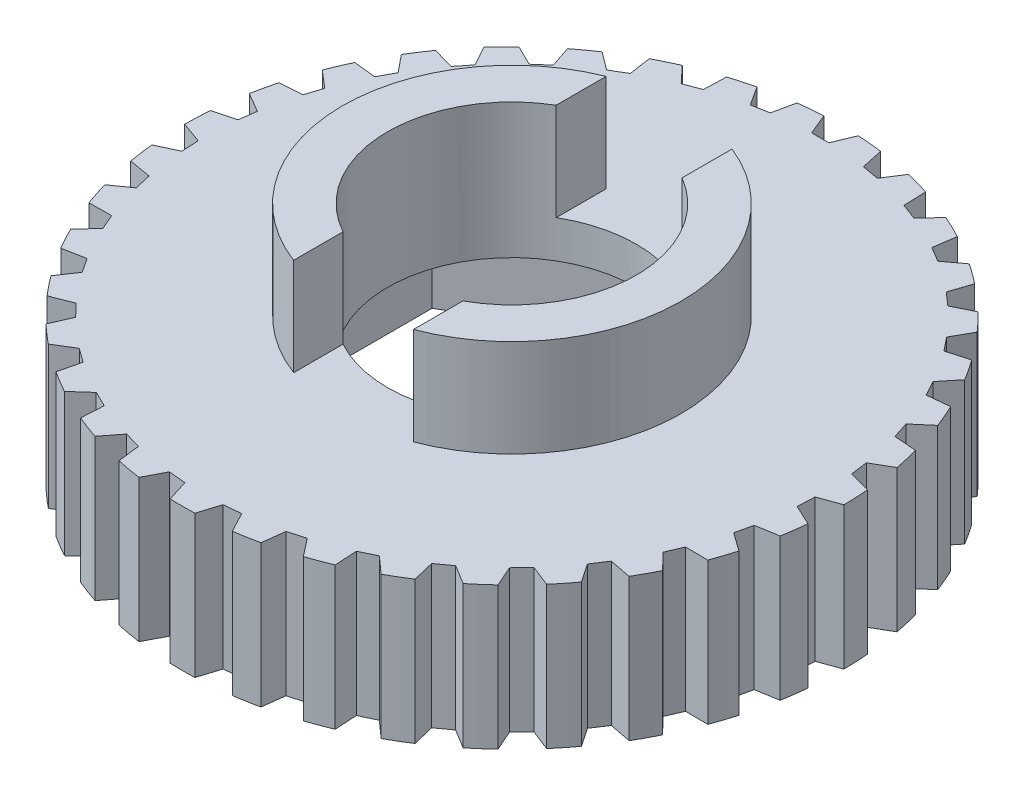
SolidWorks part; units mm, degrees
other "标注1"
sketch "草图6" plane through (10.9997, 0, -10.985) normal (0.2171, -0.5791, -0.7858) x (0.9761, 0.1195, 0.1816)
ref_plane "前视基准面" through (0, 0, 0) normal (0, 0, 1) x (1, 0, 0)
ref_plane "上视基准面" through (0, 0, 0) normal (0, 1, 0) x (1, 0, 0)
ref_plane "右视基准面" through (0, 0, 0) normal (1, 0, 0) x (0, 0, -1)
sketch "草图1" plane through (0, 0, 0) normal (0, 1, 0) x (1, 0, 0)
  circle A0 centre (0, 0) radius 5.65
  circle A1 centre (0, 0) radius 11
  circle A2 centre (0, 0) radius 4.15
  dimension "D1" = 11.3
  dimension "D2" = 22
  dimension "D3" = 1.5
extrude "凸台-拉伸1" add sketch "草图1" along normal blind 8 contours A0 A2 region at (-5.4902, 0, 0)
extrude "凸台-拉伸2" add sketch "草图1<3>" along normal blind 4.75 contours A1 A0 region at (-10.6889, 0, 0)
sketch "草图1<3>" plane through (0, 0, 0) normal (0, 1, 0) x (1, 0, 0) same geometry as "草图1"
sketch "草图2" plane through (0, 0, 0) normal (0, -1, 0) x (1, 0, 0)
  line L0 (-6, -3.4641) -> (-6, 3.4641) construction
  line L1 (-6, 3.4641) -> (0, 6.9282) construction
  line L2 (0, 6.9282) -> (6, 3.4641) construction
  line L3 (6, 3.4641) -> (6, -3.4641) construction
  line L4 (6, -3.4641) -> (0, -6.9282) construction
  line L5 (0, -6.9282) -> (-6, -3.4641) construction
  line L6 (0, -7.2746) -> (-6.3, -3.6373)
  line L7 (-6.3, -3.6373) -> (-6.3, 3.6373)
  line L8 (-6.3, 3.6373) -> (0, 7.2746)
  line L9 (0, 7.2746) -> (6.3, 3.6373)
  line L10 (6.3, 3.6373) -> (6.3, -3.6373)
  line L11 (6.3, -3.6373) -> (0, -7.2746)
  circle A0 centre (0, 0) radius 6.9282 construction
  dimension "D1" = 12
  dimension "D2" = 0.3
extrude "切除-拉伸1" cut sketch "草图2" against normal blind 3.5
sketch "草图4" plane through (0, 8, 0) normal (0, 1, 0) x (1, 0, 0)
  line L0 (0, 4.1459) -> (0, 5.647) construction
  line L1 (-2.1, 5.2452) -> (-2.1, 3.5795)
  line L2 (2.1, 5.2452) -> (2.1, 3.5795)
  line L3 (2, -3.6363) -> (2, -5.2842)
  line L4 (-2, -3.6363) -> (-2, -5.2842)
  circle A0 centre (0, 0) radius 4.15 construction
  circle A1 centre (0, 0) radius 5.65 construction
  circle A2 centre (0, 0) radius 5.65 construction
  arc A3 (-2, -3.6363) -> (2, -3.6363) centre (0, 0) ccw
  arc A4 (-2, -5.2842) -> (2, -5.2842) centre (0, 0) ccw
  arc A5 (-2.1, 5.2452) -> (-2, -5.2842) centre (0, 0) ccw construction
  arc A6 (-2.1, 3.5795) -> (-2, -3.6363) centre (0, 0) ccw construction
  arc A7 (2, -5.2842) -> (2.1, 5.2452) centre (0, 0) ccw construction
  arc A8 (2.1, 5.2452) -> (-2.1, 5.2452) centre (0, 0) ccw
  arc A9 (2, -3.6363) -> (2.1, 3.5795) centre (0, 0) ccw construction
  arc A10 (2.1, 3.5795) -> (-2.1, 3.5795) centre (0, 0) ccw
  dimension "D1" = 2.1
  dimension "D2" = 2
extrude "切除-拉伸3" cut sketch "草图4" against normal up to surface (3.25 mm away) up to face at (0, 4.75, 5.65)
sketch "草图5" plane through (0, 4.75, 0) normal (0, 1, 0) x (1, 0, 0)
  line L0 (-0.574, 10.985) -> (0, 9.5992)
  line L1 (0, 9.5992) -> (0.574, 10.985)
  line L2 (0, 9.5992) -> (0, 0) construction
  line L3 (-0.287, 10.2921) -> (0.287, 10.2921)
  circle A0 centre (0, 0) radius 11 construction
  arc A1 (0.574, 10.985) -> (-0.574, 10.985) centre (0, 0) ccw
  arc A2 (-0.574, 10.985) -> (0.574, 10.985) centre (0, 0) ccw construction
  circle M11 centre (0, 0) radius 11
  dimension "D1" = 45
  dimension "D2" = 1.5
extrude "切除-拉伸4" cut sketch "草图5" against normal blind 10 contours L0 L3 L1 M11 region at (0, 4.75, -10.683)
pattern_circular "阵列(圆周)1" count 35 over 360 about axis through (0, 4.75, 0) along (0, 1, 0) of "切除-拉伸4"
